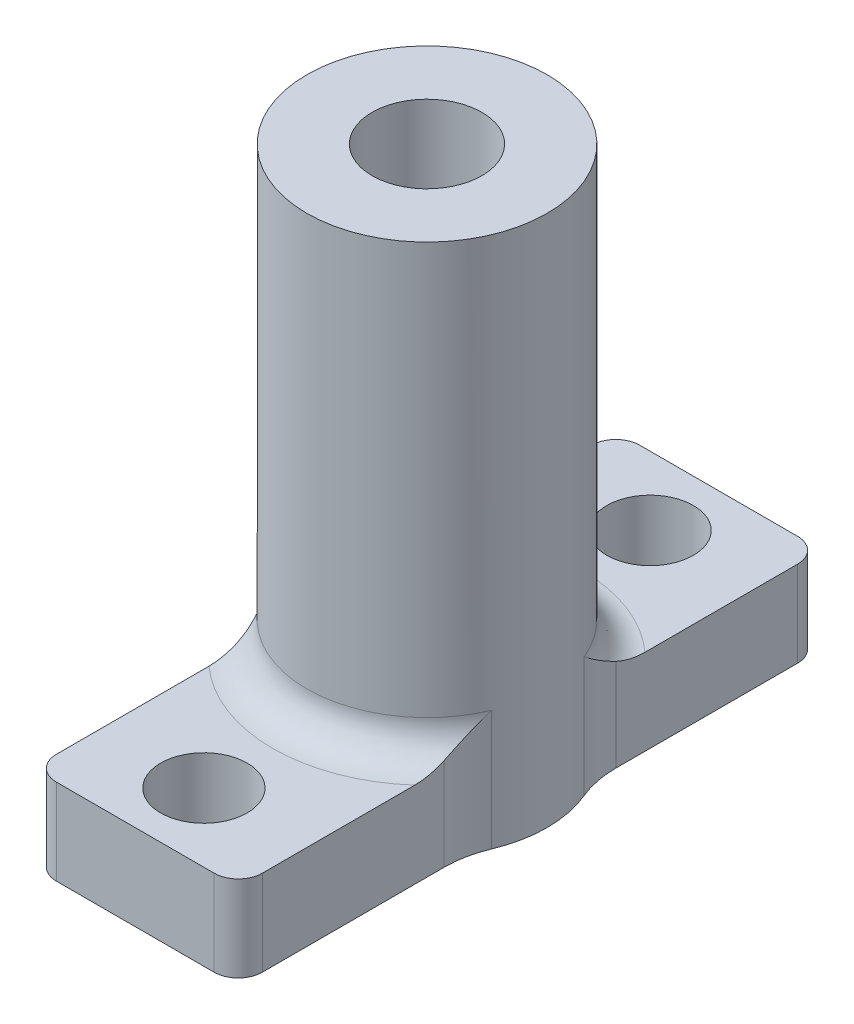
SolidWorks part; units mm, degrees
material "PLA2"
ref_plane "Front Plane" through (0, 0, 0) normal (0, 0, 1) x (1, 0, 0)
ref_plane "Top Plane" through (0, 0, 0) normal (0, 1, 0) x (1, 0, 0)
ref_plane "Right Plane" through (0, 0, 0) normal (1, 0, 0) x (0, 0, -1)
sketch "Sketch1" plane through (0, 0, 0) normal (0, 1, 0) x (1, 0, 0)
  circle A0 centre (0, 0) radius 2.032
  circle A1 centre (0, 0) radius 4.445
  dimension "D1" = 4.064
  dimension "D2" = 8.89
extrude "Boss-Extrude1" add sketch "Sketch1" along normal blind 16.51
sketch "Sketch2" plane through (0, 0, 0) normal (0, -1, 0) x (1, 0, 0)
  line L0 (0, 0) -> (0, 50000) construction
  line L1 (0, 0) -> (50000, 0) construction
  line L2 (-3.81, 2.2895) -> (-3.81, 10.795)
  line L3 (-3.81, 10.795) -> (3.81, 10.795)
  line L4 (3.81, 2.2895) -> (3.81, 10.795)
  line L5 (3.81, -2.2895) -> (3.81, -10.795)
  line L6 (-3.81, -10.795) -> (3.81, -10.795)
  line L7 (-3.81, -2.2895) -> (-3.81, -10.795)
  arc A0 (-3.81, 2.2895) -> (-3.81, -2.2895) centre (0, 0) ccw
  circle A1 centre (0, 8.255) radius 1.6002
  circle A2 centre (0, -8.255) radius 1.6002
  circle A3 centre (0, 0) radius 4.445 construction
  arc A4 (3.81, -2.2895) -> (3.81, 2.2895) centre (0, 0) ccw
  point P12 (0, 10.795)
  dimension "D1" = 3.2004
  dimension "D2" = 7.62
  dimension "D3" = 21.59
  dimension "D4" = 16.51
extrude "Boss-Extrude2" add sketch "Sketch2" along normal blind 3.175
fillet "Fillet1" radius 3.81 4 edges at (3.81, -1.5875, -2.2895) (3.81, -1.5875, 2.2895) (-3.81, -1.5875, -2.2895) (-3.81, -1.5875, 2.2895)
fillet "Fillet2" radius 1.27 2 edges at (0, 0, 4.445) (0, 0, -4.445)
fillet "Fillet3" radius 0.889 4 edges at (-3.81, -1.5875, 10.795) (3.81, -1.5875, 10.795) (3.81, -1.5875, -10.795) (-3.81, -1.5875, -10.795)
